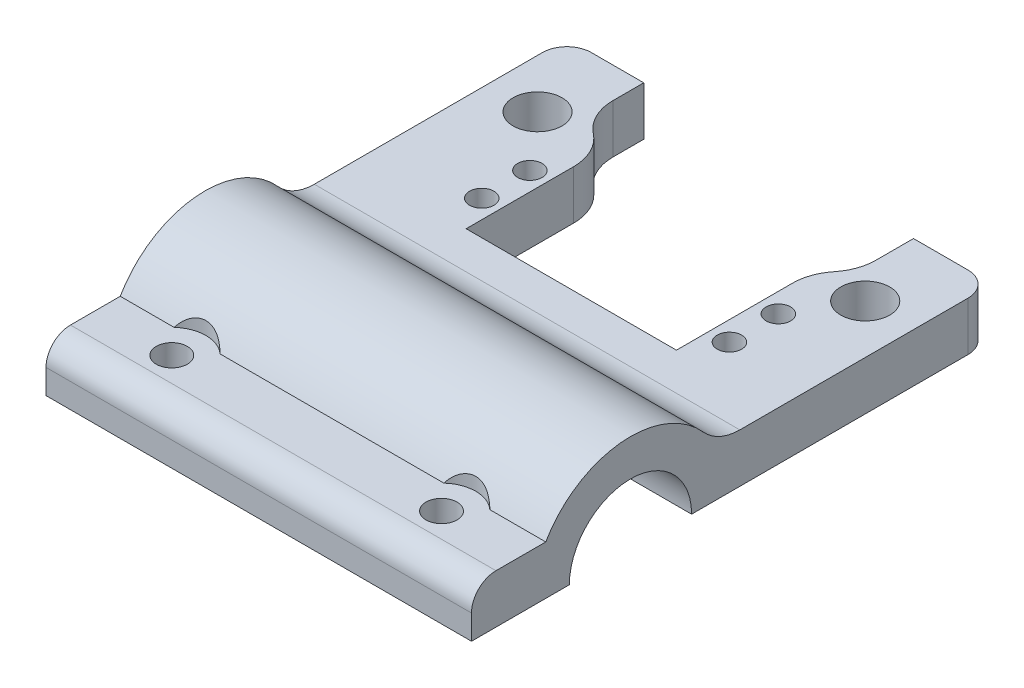
SolidWorks part; units mm, degrees
note: The reader was unsure of these and kept them because the rebuilt part matched: shared geometry of "Sketch4<4>".
ref_plane "Front Plane" through (0, 0, 0) normal (0, 0, 1) x (1, 0, 0)
ref_plane "Top Plane" through (0, 0, 0) normal (0, 1, 0) x (1, 0, 0)
ref_plane "Right Plane" through (0, 0, 0) normal (1, 0, 0) x (0, 0, -1)
sketch "Sketch1" plane through (0, 0, 0) normal (0, 1, 0) x (1, 0, 0)
  line L1 (0, 90) -> (15.7187, 90)
  line L2 (0, 90) -> (0, 0)
  line L3 (0, 0) -> (87, 0)
  line L4 (87, 90) -> (87, 0)
  line L5 (70.8704, 90) -> (87, 90)
  line L7 (15.7187, 90) -> (15.7187, 74)
  line L8 (15.7187, 74) -> (70.8704, 74)
  line L9 (70.8704, 90) -> (70.8704, 74)
  circle A0 centre (10, 74) radius 5
  circle A1 centre (77, 74) radius 5
  point P9 (52.4629, 46)
  point P26 (43.5, 0)
  dimension "D1" = 10
  dimension "D2" = 10
  dimension "D4" = 10
  dimension "D7" = 16
  dimension "D8" = 28
  dimension "D3" = 67
  dimension "D5" = 90
  dimension "D6" = 10
  dimension "D13" = 24.5371
extrude "Boss-Extrude1" add sketch "Sketch1" along normal blind 10
sketch "Sketch3" plane through (0, 10, 0) normal (0, 1, 0) x (1, 0, 0)
  line L3 (70.8704, 74) -> (15.7187, 74) construction
  line L4 (23.4, 74) -> (66.4, 74)
  line L5 (23.4, 74) -> (23.4, 46)
  line L6 (23.4, 46) -> (66.4, 46)
  line L7 (66.4, 74) -> (66.4, 46)
  circle A0 centre (70.4, 62.8367) radius 2.5
  circle A1 centre (19.6, 62.8367) radius 2.5
  circle A2 centre (19.6, 53) radius 2.5
  circle A3 centre (70.4, 52.8367) radius 2.5
  point P2 (0, 0)
  point P3 (0, 0)
  line M9 (70.8704, 74) -> (15.7187, 74)
  dimension "D2" = 50.8
  dimension "D3" = 5
  dimension "D4" = 5
  dimension "D5" = 5
  dimension "D6" = 5
  dimension "D7" = 3.8
  dimension "D8" = 10
  dimension "D9" = 28
  dimension "D11" = 4
  dimension "D12" = 21
  dimension "D13" = 43
extrude "Cut-Extrude1" cut sketch "Sketch3" against normal through all contours A2 | A0 | A3 | L7 L5 L6 M9 | A1
fillet "Fillet1" radius 10 2 edges at (70.8704, 5, -74) (15.7187, 5, -74)
fillet "Fillet2" radius 10 2 edges at (66.4, 5, -74) (23.4, 5, -74)
sketch "Sketch4" plane through (87, 0, 0) normal (1, 0, 0) x (0, 0, -1)
  line L0 (16, 0) -> (36, 0) construction
  line L2 (46, 0) -> (46, 10) construction
  line L5 (90, 10) -> (90, 0) construction
  line L6 (0, 0) -> (90, 0) construction
  circle A0 centre (16, 0) radius 12.5
  circle A1 centre (16, 0) radius 20
  point P10 (90, 5)
  line M2 (0, 0) -> (90, 0)
  line M4 (90, 10) -> (0, 10)
  line M5 (0, 10) -> (0, 0)
  dimension "D1" = 25
  dimension "D2" = 40
  dimension "D3" = 10
extrude "Boss-Extrude2" add sketch "Sketch4" against normal up to surface (87 mm away) contours A1 A0 M2 M4 | A1 A0 M4 | A1 A0 M4 M5 M2 | A1 A0 M5 M2
extrude "Cut-Extrude3" cut sketch "Sketch4<4>" against normal up to surface (87 mm away) up to face at (0, 11.25, -16)
sketch "Sketch4<4>" plane through (87, 0, 0) normal (1, 0, 0) x (0, 0, -1) same geometry as "Sketch4"
fillet "Fillet3" radius 10 1 edges at (43.5, 10, -33.3205)
sketch "Sketch8" plane through (87, 0, 0) normal (1, 0, 0) x (0, 0, -1)
  line L1 (36, 0) -> (-4, 0)
  line L2 (36, 0) -> (36, -23.2617)
  line L3 (36, -23.2617) -> (-4, -23.2617)
  line L4 (-4, 0) -> (-4, -23.2617)
  arc A0 (30.9071, 13.3333) -> (36, 0) centre (16, 0) ccw construction
extrude "Cut-Extrude8" cut sketch "Sketch8" against normal up to surface (87 mm away) up to face at (0, 0, -28.5)
sketch "Sketch9" plane through (87, 0, 0) normal (1, 0, 0) x (0, 0, -1)
  line L1 (3.5, 0) -> (-16.5, 0)
  line L2 (3.5, 0) -> (3.5, 10)
  line L3 (3.5, 10) -> (-16.5, 10)
  line L4 (-16.5, 0) -> (-16.5, 10)
  dimension "D1" = 20
  dimension "D2" = 10
extrude "Boss-Extrude3" add sketch "Sketch9" against normal up to surface (87 mm away) up to face at (0, 8.1507, -38.9032)
fillet "Fillet4" radius 5 1 edges at (43.5, 10, 16.5)
sketch "Sketch10" plane through (0, 10, 0) normal (0, 1, 0) x (1, 0, 0)
  line L0 (70.8704, 90) -> (70.8704, 82.3321) construction
  line L1 (15.7187, 83.7275) -> (15.7187, 90) construction
  line L2 (87, -16.5) -> (0, -16.5) construction
  circle A0 centre (15.7187, -6.5) radius 3.175
  circle A1 centre (70.8704, -6.5) radius 3.175
  dimension "D1" = 6.35
  dimension "D2" = 6.35
  dimension "D3" = 10
extrude "Cut-Extrude9" cut sketch "Sketch10" against normal through all
fillet "Fillet5" radius 5 2 edges at (87, 5, -90) (0, 5, -90)
sketch "Sketch11" plane through (0, 10, 0) normal (0, 1, 0) x (1, 0, 0)
  circle A0 centre (15.7187, -6.5) radius 7
  circle A1 centre (70.8704, -6.5) radius 7
  circle A2 centre (15.7187, -6.5) radius 3.175 construction
  circle A3 centre (70.8704, -6.5) radius 3.175 construction
  dimension "D1" = 14
  dimension "D2" = 14
extrude "Cut-Extrude10" cut sketch "Sketch11" along normal through all
